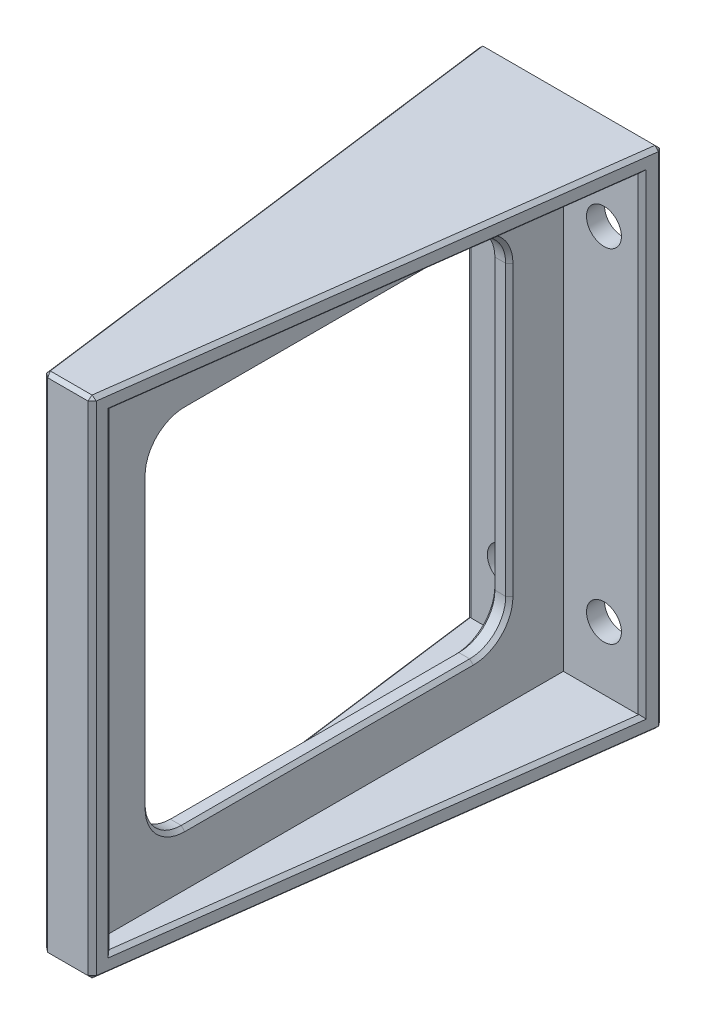
SolidWorks part; units mm, degrees
note: The reader was unsure of these and kept them because the rebuilt part matched: shared geometry of "Sketch11<2>".
material "AISI 1020 Steel, Cold Rolled"
ref_plane "Front Plane" through (0, 0, 0) normal (1, 0, 0) x (0, 1, 0)
ref_plane "Top Plane" through (0, 0, 0) normal (0, 0, 1) x (0, 1, 0)
ref_plane "Right Plane" through (0, 0, 0) normal (0, 1, 0) x (-1, 0, 0)
sketch "Sketch1" plane through (0, 0, 0) normal (0, 1, 0) x (-1, 0, 0)
  line L0 (0, 88.9) -> (0, -88.9) construction
  line L1 (31.75, -88.9) -> (-31.75, -88.9)
  line L2 (-8.4667, 88.9) -> (8.4667, 88.9)
  line L3 (-8.4667, 88.9) -> (-31.75, -88.9)
  line L4 (8.4667, 88.9) -> (31.75, -88.9)
  point P3 (0, 0)
  point P7 (0, 88.9)
  point P54 (0, -88.9)
  dimension "D1" = 177.8
  dimension "D2" = 63.5
  dimension "D3" = 16.9333
extrude "Boss-Extrude1" add sketch "Sketch1" along normal mid plane 177.8 contours L4 L1 L3 L2
sketch "Sketch11" plane through (0, 0, 0) normal (1, 0, 0) x (0, 1, 0)
  line L0 (88.9, -88.9) -> (-88.9, -88.9) construction
  line L1 (-82.55, 82.55) -> (82.55, 82.55)
  line L2 (-82.55, 82.55) -> (-82.55, -82.55)
  line L3 (-82.55, -82.55) -> (82.55, -82.55)
  line L4 (82.55, 82.55) -> (82.55, -82.55)
  line L5 (-82.55, 82.55) -> (82.55, -82.55) construction
  line L6 (-82.55, -82.55) -> (82.55, 82.55) construction
  line L7 (88.9, 88.9) -> (88.9, -88.9) construction
  point P0 (0, 0)
  dimension "D1" = 6.35
  dimension "D2" = 6.35
sketch "Sketch12" plane through (0, 0, 0) normal (1, 0, 0) x (0, 1, 0)
  line L1 (-63.5, 63.5) -> (63.5, 63.5)
  line L2 (-63.5, 63.5) -> (-63.5, -63.5)
  line L3 (-63.5, -63.5) -> (63.5, -63.5)
  line L4 (63.5, 63.5) -> (63.5, -63.5)
  line L5 (-63.5, 63.5) -> (63.5, -63.5) construction
  line L6 (-63.5, -63.5) -> (63.5, 63.5) construction
  point P0 (0, 0)
  dimension "D1" = 127
  dimension "D2" = 127
extrude "Cut-Extrude2" cut sketch "Sketch12" against normal through all both and the other way through all
extrude "Cut-Extrude3" cut sketch "Sketch11" against normal through all from offset 3.175 offset against normal yes
extrude "Cut-Extrude4" cut sketch "Sketch11<2>" along normal through all from offset 3.175
sketch "Sketch11<2>" plane through (0, 0, 0) normal (1, 0, 0) x (0, 1, 0) same geometry as "Sketch11"
fillet "Fillet3" radius 12.7 4 edges at (0, 63.5, 63.5) (0, -63.5, 63.5) (0, -63.5, -63.5) (0, 63.5, -63.5)
hole_wizard "9/16-12 Tapped Hole1" positions "Sketch17" profile "Sketch18" tap size "9/16-12" standard "ANSI Inch" end condition up to next
sketch "Sketch17" plane through (0, 0, -88.9) normal (0, 0, -1) x (1, 0, 0)
  line L1 (-31.75, 88.9) -> (31.75, 88.9) construction
  line L4 (0, 0) -> (0, -50000) construction
  line L7 (-3.175, -60.325) -> (-31.75, -60.325) construction
  line L8 (-31.75, -88.9) -> (-31.75, 88.9) construction
  line L10 (3.175, -60.325) -> (31.75, -60.325) construction
  line L11 (31.75, -88.9) -> (31.75, 88.9) construction
  line L12 (-31.75, -88.9) -> (31.75, -88.9) construction
  line L13 (-31.75, 60.325) -> (-17.4625, 60.325)
  line L14 (-17.4625, 60.325) -> (17.4625, 60.325)
  line L15 (17.4625, 60.325) -> (31.75, 60.325)
  line L16 (-3.175, 0) -> (-3.175, -50000) construction
  line L17 (3.175, 0) -> (3.175, -50000) construction
  point P20 (-17.4625, 60.325)
  point P38 (17.4625, 60.325)
  point P39 (17.4625, -60.325)
  point P40 (-17.4625, -60.325)
  point P82 (0, 0)
  point P87 (0, 0)
  dimension "D3" = 2
  dimension "D1" = 28.575
  dimension "D2" = 28.575
  dimension "D5" = 14.2875
  dimension "D6" = 3.175
  dimension "D7" = 3.175
  dimension "D4" = 2
sketch "Sketch18" plane through (-17.4625, -60.325, -88.9) normal (1, 0, 0) x (0, 1, 0)
  line L0 (0, 0) -> (0, 6.35)
  line L1 (0, 6.35) -> (6.1519, 6.35)
  line L2 (6.1519, 6.35) -> (6.1519, 0)
  line L5 (6.1519, 0) -> (0, 0)
  line L11 (0, -6.35) -> (0, 107.95) construction
  dimension "Thru Tap Drill Dia." = 12.3038
  dimension "Thru Tap Drill Depth" = 6.35
chamfer "Chamfer2" distance 1.27 angle 45 36 edges at (9.2982, 0, 82.55) (20.1083, -82.55, 0) (30.9185, 0, -82.55) (20.1083, 82.55, 0) (8.4667, 0, 88.9) (20.1083, 88.9, 0) (31.75, 0, -88.9) (20.1083, -88.9, 0) (-31.75, 0, -88.9) (-20.1083, 88.9, 0) (-8.4667, 0, 88.9) (-20.1083, -88.9, 0) (-30.9185, 0, -82.55) (-20.1083, -82.55, 0) (-9.2982, 0, 82.55) (-20.1083, 82.55, 0) (-3.175, 59.7803, 59.7803) (-3.175, 63.5, 0) (-3.175, 59.7803, -59.7803) (-3.175, 0, -63.5) (-3.175, -59.7803, -59.7803) (-3.175, -63.5, 0) (-3.175, -59.7803, 59.7803) (-3.175, 0, 63.5) (3.175, -59.7803, 59.7803) (3.175, -63.5, 0) (3.175, -59.7803, -59.7803) (3.175, 0, -63.5) (3.175, 59.7803, -59.7803) (3.175, 63.5, 0) (3.175, 59.7803, 59.7803) (3.175, 0, 63.5) (0, 88.9, -88.9) (0, 88.9, 88.9) (0, -88.9, -88.9) (0, -88.9, 88.9)
